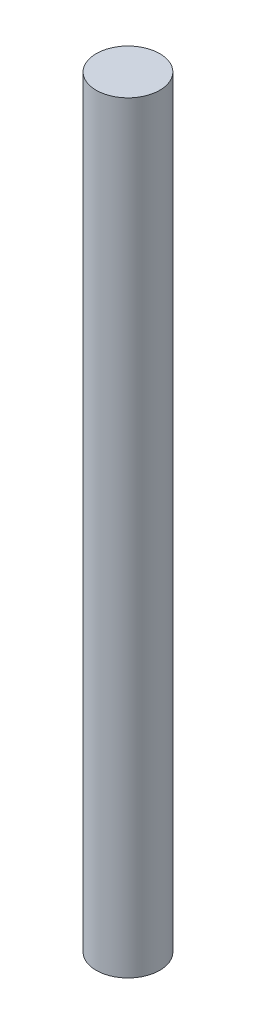
SolidWorks part; units mm, degrees
ref_plane "Front Plane" through (0, 0, 0) normal (0, 0, 1) x (1, 0, 0)
ref_plane "Top Plane" through (0, 0, 0) normal (0, 1, 0) x (1, 0, 0)
ref_plane "Right Plane" through (0, 0, 0) normal (1, 0, 0) x (0, 0, -1)
sketch "Sketch1" plane through (0, 0, 0) normal (0, 1, 0) x (1, 0, 0)
  circle A0 centre (0, 0) radius 2.5
  dimension "D1" = 5
extrude "Boss-Extrude1" add sketch "Sketch1" along normal blind 60
